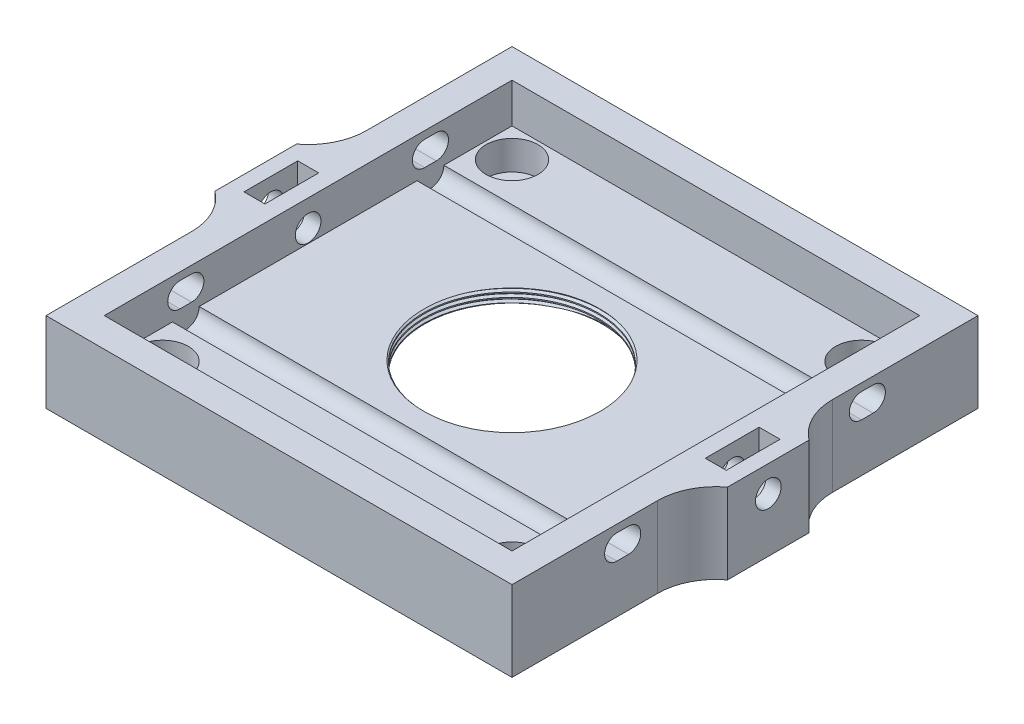
SolidWorks part; units mm, degrees
ref_plane "Front Plane" through (0, 0, 0) normal (0, 0, 1) x (1, 0, 0)
ref_plane "Top Plane" through (0, 0, 0) normal (0, 1, 0) x (1, 0, 0)
ref_plane "Right Plane" through (0, 0, 0) normal (1, 0, 0) x (0, 0, -1)
sketch "Sketch1" plane through (0, 0, 0) normal (0, 1, 0) x (1, 0, 0)
  line L1 (-20, -20) -> (20, -20)
  line L2 (-20, -20) -> (-20, 20)
  line L3 (-20, 20) -> (20, 20)
  line L4 (20, -20) -> (20, 20)
  line L5 (-20, -20) -> (20, 20) construction
  line L6 (-20, 20) -> (20, -20) construction
  point P0 (0, 0)
  dimension "D1" = 40
  dimension "D2" = 40
extrude "Boss-Extrude1" add sketch "Sketch1" along normal blind 3.5
sketch "Sketch2" plane through (0, 3.5, 0) normal (0, 1, 0) x (1, 0, 0)
  line L6 (-20, -20) -> (20, -20)
  line L7 (-20, -20) -> (-20, 20)
  line L12 (-20, 20) -> (20, 20)
  line L13 (20, -20) -> (20, 20)
  line L22 (-17.5, -17.5) -> (17.5, -17.5)
  line L23 (-17.5, -17.5) -> (-17.5, 17.5)
  line L28 (-17.5, 17.5) -> (17.5, 17.5)
  line L29 (17.5, -17.5) -> (17.5, 17.5)
  line L38 (-17.5, -17.5) -> (17.5, 17.5) construction
  line L39 (-17.5, 17.5) -> (17.5, -17.5) construction
  line L40 (-20, -20) -> (15, -20)
  line L41 (-20, -20) -> (-20, 15)
  line L69 (-20, -20) -> (-20, -15)
  dimension "D1" = 2.5
  dimension "D2" = 2.5
extrude "Boss-Extrude2" add sketch "Sketch2" along normal blind 3.4
sketch "Sketch7" plane through (0, 3.5, 0) normal (0, 1, 0) x (1, 0, 0)
  line L1 (17.5, -17.5) -> (-17.5, -17.5)
  line L2 (17.5, -17.5) -> (17.5, 17.5)
  line L3 (17.5, 17.5) -> (-17.5, 17.5)
  line L4 (-17.5, -17.5) -> (-17.5, 17.5)
  line L5 (17.5, -17.5) -> (-17.5, 17.5) construction
  line L6 (17.5, 17.5) -> (-17.5, -17.5) construction
  circle A0 centre (0, 0) radius 7.5
  point P0 (0, 0)
  dimension "D1" = 15
extrude "Cut-Extrude5" cut sketch "Sketch7" against normal through all contours A0
sketch "Sketch8" plane through (0, 0, 0) normal (0, -1, 0) x (1, 0, 0)
  line L1 (-15, 15) -> (15, 15)
  line L2 (-15, 15) -> (-15, -15)
  line L3 (-15, -15) -> (15, -15)
  line L4 (15, 15) -> (15, -15)
  line L5 (-15, 15) -> (15, -15) construction
  line L6 (-15, -15) -> (15, 15) construction
  line L7 (-13.0659, 15) -> (-14.0329, 16.675)
  line L8 (-14.0329, 16.675) -> (-15.9671, 16.675)
  line L9 (-15.9671, 16.675) -> (-16.9341, 15)
  line L10 (-16.9341, 15) -> (-15.9671, 13.325)
  line L11 (-15.9671, 13.325) -> (-14.0329, 13.325)
  line L12 (-14.0329, 13.325) -> (-13.0659, 15)
  line L13 (13.0659, 15) -> (14.0329, 13.325)
  line L14 (14.0329, 13.325) -> (15.9671, 13.325)
  line L15 (15.9671, 13.325) -> (16.9341, 15)
  line L16 (16.9341, 15) -> (15.9671, 16.675)
  line L17 (15.9671, 16.675) -> (14.0329, 16.675)
  line L18 (14.0329, 16.675) -> (13.0659, 15)
  line L19 (13.0659, -15) -> (14.0329, -16.675)
  line L20 (14.0329, -16.675) -> (15.9671, -16.675)
  line L21 (15.9671, -16.675) -> (16.9341, -15)
  line L22 (16.9341, -15) -> (15.9671, -13.325)
  line L23 (15.9671, -13.325) -> (14.0329, -13.325)
  line L24 (14.0329, -13.325) -> (13.0659, -15)
  line L25 (-13.0659, -15) -> (-14.0329, -13.325)
  line L26 (-14.0329, -13.325) -> (-15.9671, -13.325)
  line L27 (-15.9671, -13.325) -> (-16.9341, -15)
  line L28 (-16.9341, -15) -> (-15.9671, -16.675)
  line L29 (-15.9671, -16.675) -> (-14.0329, -16.675)
  line L30 (-14.0329, -16.675) -> (-13.0659, -15)
  circle A0 centre (-15, 15) radius 1.675 construction
  circle A1 centre (15, 15) radius 1.675 construction
  circle A2 centre (15, -15) radius 1.675 construction
  circle A3 centre (-15, -15) radius 1.675 construction
  point P0 (0, 0)
  point P6 (-16.4506, -14.1625)
  dimension "D1" = 30
  dimension "D2" = 30
  dimension "D3" = 3.35
  dimension "D4" = 3.35
  dimension "D5" = 3.35
  dimension "D6" = 3.35
sketch "Sketch9" plane through (0, 3.5, 0) normal (0, 1, 0) x (1, 0, 0)
  line L1 (-15, -15) -> (15, -15)
  line L2 (-15, -15) -> (-15, 15)
  line L3 (-15, 15) -> (15, 15)
  line L4 (15, -15) -> (15, 15)
  line L5 (-15, -15) -> (15, 15) construction
  line L6 (-15, 15) -> (15, -15) construction
  circle A0 centre (-15, 15) radius 2.225
  circle A1 centre (15, 15) radius 2.225
  circle A2 centre (-15, -15) radius 2.225
  circle A3 centre (15, -15) radius 2.225
  point P0 (0, 0)
  dimension "D2" = 4.45
  dimension "D3" = 4.45
  dimension "D4" = 4.45
  dimension "D5" = 4.45
  dimension "D1" = 30
extrude "Cut-Extrude6" cut sketch "Sketch9" against normal blind 2.5
sketch "Sketch10" plane through (0, 3.5, 0) normal (0, 1, 0) x (1, 0, 0)
  line L1 (-15, -15) -> (15, -15)
  line L2 (-15, -15) -> (-15, 15)
  line L3 (-15, 15) -> (15, 15)
  line L4 (15, -15) -> (15, 15)
  line L5 (-15, -15) -> (15, 15) construction
  line L6 (-15, 15) -> (15, -15) construction
  circle A0 centre (-15, 15) radius 1.35
  circle A1 centre (15, 15) radius 1.35
  circle A2 centre (15, -15) radius 1.35
  circle A3 centre (-15, -15) radius 1.35
  point P0 (0, 0)
  dimension "D3" = 2.7
  dimension "D4" = 2.7
  dimension "D5" = 2.7
  dimension "D6" = 2.7
  dimension "D1" = 30
  dimension "D2" = 30
extrude "Cut-Extrude7" cut sketch "Sketch10" against normal through all contours A0 | A1 | A2 | A3
sketch "Sketch12" plane through (0, 3.5, 0) normal (0, 1, 0) x (1, 0, 0)
  line L0 (0, 6.9) -> (0, 13.1)
  line L1 (0, 10) -> (-8.6603, -5)
  line L2 (-8.6603, -5) -> (8.6603, -5)
  line L3 (8.6603, -5) -> (0, 10)
  line L4 (8.6603, -8.1) -> (8.6603, -1.9)
  line L5 (-8.6603, -1.9) -> (-8.6603, -8.1)
  line L6 (0, 6.9) -> (0, 13.1) construction
  line L7 (-1, 6.9) -> (-1, 13.1)
  line L8 (1, 6.9) -> (1, 13.1)
  line L9 (8.6603, -8.1) -> (8.6603, -1.9) construction
  line L10 (7.6603, -8.1) -> (7.6603, -1.9)
  line L11 (9.6603, -8.1) -> (9.6603, -1.9)
  line L12 (-8.6603, -1.9) -> (-8.6603, -7.7468) construction
  line L13 (-7.6603, -1.9) -> (-7.6603, -7.7468)
  line L14 (-9.6603, -1.9) -> (-9.6603, -7.7468)
  circle A0 centre (0, 0) radius 5 construction
  arc A1 (-1, 6.9) -> (1, 6.9) centre (0, 6.9) ccw
  arc A2 (1, 13.1) -> (-1, 13.1) centre (0, 13.1) ccw
  arc A3 (7.6603, -8.1) -> (9.6603, -8.1) centre (8.6603, -8.1) ccw
  arc A4 (9.6603, -1.9) -> (7.6603, -1.9) centre (8.6603, -1.9) ccw
  arc A5 (-7.6603, -1.9) -> (-9.6603, -1.9) centre (-8.6603, -1.9) ccw
  arc A6 (-9.6603, -7.7468) -> (-7.6603, -7.7468) centre (-8.6603, -7.7468) ccw
  point P9 (0, 10)
  point P12 (8.6603, -5)
  point P14 (-8.6603, -5)
  point P15 (0, 10)
  point P20 (8.6603, -5)
  point P25 (-8.6603, -4.8234)
  dimension "D1" = 10
  dimension "D2" = 6.2
  dimension "D3" = 6.2
  dimension "D4" = 6.2
  dimension "D5" = 2
  dimension "D6" = 2
  dimension "D7" = 2
sketch "Sketch13" plane through (0, 0, 0) normal (0, -1, 0) x (1, 0, 0)
  line L1 (-20, -20) -> (20, -20)
  line L2 (-20, -20) -> (-20, 20)
  line L3 (-20, 20) -> (20, 20)
  line L4 (20, -20) -> (20, 20)
  line L5 (-20, -20) -> (20, 20) construction
  line L6 (-20, 20) -> (20, -20) construction
  line L7 (-22, -3.5) -> (22, -3.5)
  line L8 (-22, -3.5) -> (-22, 3.5)
  line L9 (-22, 3.5) -> (22, 3.5)
  line L10 (22, -3.5) -> (22, 3.5)
  line L11 (-22, -3.5) -> (22, 3.5) construction
  line L12 (-22, 3.5) -> (22, -3.5) construction
  point P0 (0, 0)
  point P7 (0, 0)
  dimension "D1" = 2
  dimension "D2" = 7
extrude "Boss-Extrude3" add sketch "Sketch13" against normal up to surface (6.9 mm away) contours L7 L10 L9 L4 | L9 L8 L7 L2
sketch "Sketch11" plane through (-17.5, 0, 0) normal (1, 0, 0) x (0, 0, -1)
  line L0 (-17.5, 6.9) -> (-17.5, 5.2)
  line L1 (-17.5, 3.5) -> (17.5, 3.5)
  line L2 (-17.5, 3.5) -> (-17.5, 6.9)
  line L3 (-17.5, 6.9) -> (17.5, 6.9)
  line L4 (17.5, 3.5) -> (17.5, 6.9)
  line L5 (-17.5, 5.2) -> (-10.5, 5.2)
  line L6 (17.5, 6.9) -> (17.5, 5.2)
  line L7 (17.5, 5.2) -> (10.5, 5.2)
  line L8 (-11, 5.2) -> (-10, 5.2)
  line L9 (-10, 5.2) -> (10.5, 5.2)
  line L10 (10, 5.2) -> (11, 5.2)
  line L11 (-11, 5.2) -> (-10, 5.2) construction
  line L12 (-11, 6.25) -> (-10, 6.25)
  line L13 (-11, 4.15) -> (-10, 4.15)
  line L14 (10, 5.2) -> (11, 5.2) construction
  line L15 (10, 6.25) -> (11, 6.25)
  line L16 (10, 4.15) -> (11, 4.15)
  circle A0 centre (-10.5, 5.2) radius 1.15
  circle A1 centre (10.5, 5.2) radius 1.15
  arc A2 (-11, 6.25) -> (-11, 4.15) centre (-11, 5.2) ccw
  arc A3 (-10, 4.15) -> (-10, 6.25) centre (-10, 5.2) ccw
  arc A4 (10, 6.25) -> (10, 4.15) centre (10, 5.2) ccw
  arc A5 (11, 4.15) -> (11, 6.25) centre (11, 5.2) ccw
  circle A6 centre (0.25, 5.2) radius 0.975
  point P12 (-10.5, 5.2)
  point P15 (-10.5, 5.2)
  point P18 (10.5, 5.2)
  point P23 (10.5, 5.2)
  dimension "D3" = 2.3
  dimension "D4" = 2.3
  dimension "D9" = 1.95
  dimension "D1" = 7
  dimension "D2" = 7
  dimension "D5" = 1
  dimension "D6" = 1
  dimension "D7" = 2.1
  dimension "D8" = 2.1
extrude "Cut-Extrude8" cut sketch "Sketch11" against normal through all both and the other way through all
ref_plane "Plane1" through (20, 6.9, 3.5) normal (0, -1, 0) x (-1, 0, 0)
sketch "Sketch14" plane through (-22, 0, 0) normal (-1, 0, 0) x (0, 0, 1)
  line L0 (-3.5, 6.9) -> (3.5, 6.9) construction
  line L1 (2.3094, 4.65) -> (1.1547, 6.65)
  line L2 (1.1547, 6.65) -> (-1.1547, 6.65)
  line L3 (-1.1547, 6.65) -> (-2.3094, 4.65)
  line L4 (-2.3094, 4.65) -> (-1.1547, 2.65)
  line L5 (-1.1547, 2.65) -> (1.1547, 2.65)
  line L6 (1.1547, 2.65) -> (2.3094, 4.65)
  line L8 (-1.1547, 6.65) -> (1.1547, 6.65)
  line L9 (-1.1547, 6.65) -> (-1.1547, 6.9)
  line L10 (-1.1547, 6.9) -> (1.1547, 6.9)
  line L11 (1.1547, 6.65) -> (1.1547, 6.9)
  circle A0 centre (0, 4.65) radius 2 construction
  dimension "D1" = 0.25
  dimension "D2" = 4
sketch "Sketch15" plane through (22, 0, 0) normal (1, 0, 0) x (0, 0, -1)
  line L0 (3.5, 6.9) -> (-3.5, 6.9) construction
  line L1 (2.3094, 4.65) -> (1.1547, 6.65)
  line L2 (1.1547, 6.65) -> (-1.1547, 6.65)
  line L3 (-1.1547, 6.65) -> (-2.3094, 4.65)
  line L4 (-2.3094, 4.65) -> (-1.1547, 2.65)
  line L5 (-1.1547, 2.65) -> (1.1547, 2.65)
  line L6 (1.1547, 2.65) -> (2.3094, 4.65)
  line L8 (-1.1547, 6.65) -> (1.1547, 6.65)
  line L9 (-1.1547, 6.65) -> (-1.1547, 6.9)
  line L10 (-1.1547, 6.9) -> (1.1547, 6.9)
  line L11 (1.1547, 6.65) -> (1.1547, 6.9)
  circle A0 centre (0, 4.65) radius 2 construction
  dimension "D1" = 0.25
  dimension "D2" = 4
fillet "Fillet1" radius 5 12 edges at (-21, 0, 3.5) (-20, 3.45, 3.5) (-21, 6.9, -3.5) (-20, 3.45, -3.5) (-21, 0, -3.5) (-21, 6.9, 3.5) (21, 6.9, 3.5) (21, 0, -3.5) (20, 3.45, 3.5) (21, 0, 3.5) (20, 3.45, -3.5) (21, 6.9, -3.5)
chamfer "Chamfer1" distance 2.5 angle 65 1 edges at (0, 0, 7.5)
sketch "Sketch20" plane through (0, 0, 0) normal (0, 0, 1) x (1, 0, 0)
  line L0 (-7.4962, 2.5) -> (-12.8575, 0)
  line L1 (7.5, 2.5) -> (-7.5, 2.5) construction
  line L2 (-12.8613, 0) -> (12.8613, 0) construction
  line L3 (20, 0) -> (-20, 0) construction
  line L4 (-12.8575, 0) -> (-12.772, 0.2349)
  line L5 (-12.772, 0.2349) -> (-12.537, 0.1494)
  line L6 (-12.5402, 0.1479) -> (-12.4547, 0.3828)
  line L7 (-12.4547, 0.3828) -> (-12.2198, 0.2973)
  line L8 (0, 0) -> (0, 50000) construction
  line L9 (-12.223, 0.2958) -> (-12.1375, 0.5308)
  line L10 (-12.1375, 0.5308) -> (-11.9026, 0.4453)
  line L11 (-7.4962, 2.5) -> (-7.4617, 2.5161)
  line L12 (-11.9058, 0.4437) -> (-11.8203, 0.6787)
  line L13 (-11.8203, 0.6787) -> (-11.5854, 0.5932)
  line L15 (-11.5886, 0.5917) -> (-11.5031, 0.8266)
  line L16 (-11.5031, 0.8266) -> (-11.2682, 0.7411)
  line L18 (-11.2714, 0.7396) -> (-11.1859, 0.9745)
  line L19 (-11.1859, 0.9745) -> (-10.951, 0.889)
  line L21 (-10.9542, 0.8875) -> (-10.8687, 1.1224)
  line L22 (-10.8687, 1.1224) -> (-10.6338, 1.0369)
  line L24 (-10.637, 1.0354) -> (-10.5515, 1.2703)
  line L25 (-10.5515, 1.2703) -> (-10.3166, 1.1848)
  line L27 (-10.3198, 1.1833) -> (-10.2343, 1.4183)
  line L28 (-10.2343, 1.4183) -> (-9.9994, 1.3327)
  line L30 (-10.0026, 1.3312) -> (-9.9171, 1.5662)
  line L31 (-9.9171, 1.5662) -> (-9.6822, 1.4807)
  line L33 (-9.6854, 1.4792) -> (-9.5999, 1.7141)
  line L34 (-9.5999, 1.7141) -> (-9.365, 1.6286)
  line L36 (-9.3682, 1.6271) -> (-9.2827, 1.862)
  line L37 (-9.2827, 1.862) -> (-9.0477, 1.7765)
  line L39 (-9.051, 1.775) -> (-8.9655, 2.0099)
  line L40 (-8.9655, 2.0099) -> (-8.7305, 1.9244)
  line L42 (-8.7338, 1.9229) -> (-8.6483, 2.1578)
  line L43 (-8.6483, 2.1578) -> (-8.4133, 2.0723)
  line L45 (-8.4165, 2.0708) -> (-8.331, 2.3058)
  line L46 (-8.331, 2.3058) -> (-8.0961, 2.2202)
  line L48 (-8.0993, 2.2187) -> (-8.0138, 2.4537)
  line L49 (-8.0138, 2.4537) -> (-7.7789, 2.3682)
  line L51 (-7.7821, 2.3667) -> (-7.6966, 2.6016)
  line L52 (-7.6966, 2.6016) -> (-7.4617, 2.5161)
  line L54 (-7.179, 2.6479) -> (-12.5402, 0.1479) [skipped]
  line L55 (-6.8618, 2.7958) -> (-12.223, 0.2958) [skipped]
  line L56 (-6.5446, 2.9437) -> (-11.9058, 0.4437) [skipped]
  line L57 (-6.2274, 3.0917) -> (-11.5886, 0.5917) [skipped]
  line L58 (-5.9102, 3.2396) -> (-11.2714, 0.7396) [skipped]
  line L59 (-5.5929, 3.3875) -> (-10.9542, 0.8875) [skipped]
  line L60 (-5.2757, 3.5354) -> (-10.637, 1.0354) [skipped]
  line L61 (-4.9585, 3.6833) -> (-10.3198, 1.1833) [skipped]
  line L62 (-4.6413, 3.8312) -> (-10.0026, 1.3312) [skipped]
  line L63 (-4.3241, 3.9792) -> (-9.6854, 1.4792) [skipped]
  line L64 (-4.0069, 4.1271) -> (-9.3682, 1.6271) [skipped]
  line L65 (-3.6897, 4.275) -> (-9.051, 1.775) [skipped]
  line L66 (-3.3725, 4.4229) -> (-8.7338, 1.9229) [skipped]
  line L67 (-3.0553, 4.5708) -> (-8.4165, 2.0708) [skipped]
  line L68 (-2.7381, 4.7187) -> (-8.0993, 2.2187) [skipped]
  line L69 (-2.4209, 4.8667) -> (-7.7821, 2.3667) [skipped]
  dimension "D1" = 0.25
  dimension "D2" = 45
  dimension "D3" = 17
revolve "Cut-Revolve3" cut sketch "Sketch20" angle 360 about L8
thread "Thread1" pitch 0.4 start angle 0, offset 1, length 3, pitch 0.4, diameter 15
ref_plane "Plane3" through (-7.5, 4.5, 0) normal (0, 0, 1) x (-1, 0, 0)
sketch "Thread Profile2" plane through (-7.5, 4.5, 0) normal (0, 0, 1) x (-1, 0, 0)
  line L0 (0, 0) -> (0, 0.4) construction
  line L1 (0, 0) -> (0.2165, 0.125)
  line L2 (0.2165, 0.125) -> (0.2165, 0.175)
  line L3 (0.2165, 0.175) -> (0, 0.3)
  line L4 (0.2165, 0.15) -> (0, 0.15) construction
  line L11 (0, 0) -> (0, 0.3)
  point P2 (0, 0)
  dimension "Pitch" = 0.4
  dimension "Profile_Angle" = 60
  dimension "Profile_Land" = 0.05
  dimension "Profile_Height" = 0.2165
sketch "Sketch24" plane through (-20, 0, 0) normal (-1, 0, 0) x (0, 0, 1)
  line L1 (2.3094, 4.65) -> (1.1547, 6.65)
  line L2 (1.1547, 6.65) -> (-1.1547, 6.65)
  line L3 (-1.1547, 6.65) -> (-2.3094, 4.65)
  line L4 (-2.3094, 4.65) -> (-1.1547, 2.65)
  line L5 (-1.1547, 2.65) -> (1.1547, 2.65)
  line L6 (1.1547, 2.65) -> (2.3094, 4.65)
  circle A0 centre (0, 4.65) radius 2 construction
  dimension "D1" = 4
extrude "Cut-Extrude12" cut sketch "Sketch24" against normal blind 1.1 and the other way blind 0.7
sketch "Sketch25" plane through (0, 6.9, 0) normal (0, 1, 0) x (1, 0, 0)
  line L0 (0, 20) -> (0, -49980) construction
  line L1 (-20, 20) -> (20, 20)
  line L2 (-20, 20) -> (-20, -20)
  line L3 (-20, -20) -> (20, -20)
  line L4 (20, 20) -> (20, -20)
  line L5 (-20.7, 2.3094) -> (-18.9, 2.3094)
  line L6 (-20.7, 2.3094) -> (-20.7, -2.3094)
  line L7 (-20.7, -2.3094) -> (-18.9, -2.3094)
  line L8 (-18.9, 2.3094) -> (-18.9, -2.3094)
  line L9 (18.9, 2.3094) -> (18.9, -2.3094)
  line L10 (20.7, -2.3094) -> (18.9, -2.3094)
  line L11 (20.7, 2.3094) -> (20.7, -2.3094)
  line L12 (20.7, 2.3094) -> (18.9, 2.3094)
  point P14 (0, 20)
  point P15 (0, -20)
extrude "Cut-Extrude13" cut sketch "Sketch25" against normal blind 2.25 contours L8 L5 L2 L7 | L6 L7 L2 L5 | L11 L10 L9 L12
sketch "Sketch26" plane through (20, 0, 0) normal (1, 0, 0) x (0, 0, -1)
  line L1 (2.3094, 4.65) -> (1.1547, 6.65)
  line L2 (1.1547, 6.65) -> (-1.1547, 6.65)
  line L3 (-1.1547, 6.65) -> (-2.3094, 4.65)
  line L4 (-2.3094, 4.65) -> (-1.1547, 2.65)
  line L5 (-1.1547, 2.65) -> (1.1547, 2.65)
  line L6 (1.1547, 2.65) -> (2.3094, 4.65)
  circle A0 centre (0, 4.65) radius 2 construction
extrude "Cut-Extrude14" cut sketch "Sketch26" against normal blind 1.1 and the other way blind 0.7
sketch "Sketch27" plane through (18.9, 0, 0) normal (1, 0, 0) x (0, 0, -1)
  circle A0 centre (0, 4.65) radius 1.1
  dimension "D1" = 2.2
extrude "Cut-Extrude15" cut sketch "Sketch27" against normal through all and the other way through all
sketch "Sketch28" plane through (-17.5, 0, 0) normal (1, 0, 0) x (0, 0, -1)
  line L0 (-17.5, 3.5) -> (17.5, 3.5) construction
  circle A0 centre (-10.5, 3.5) radius 1.15
  circle A1 centre (10.5, 3.5) radius 1.15
  dimension "D1" = 2.3
  dimension "D2" = 2.3
extrude "Cut-Extrude16" cut sketch "Sketch28" along normal up to surface (35 mm away) up to face at (17.5, 4.65, 1.1)
